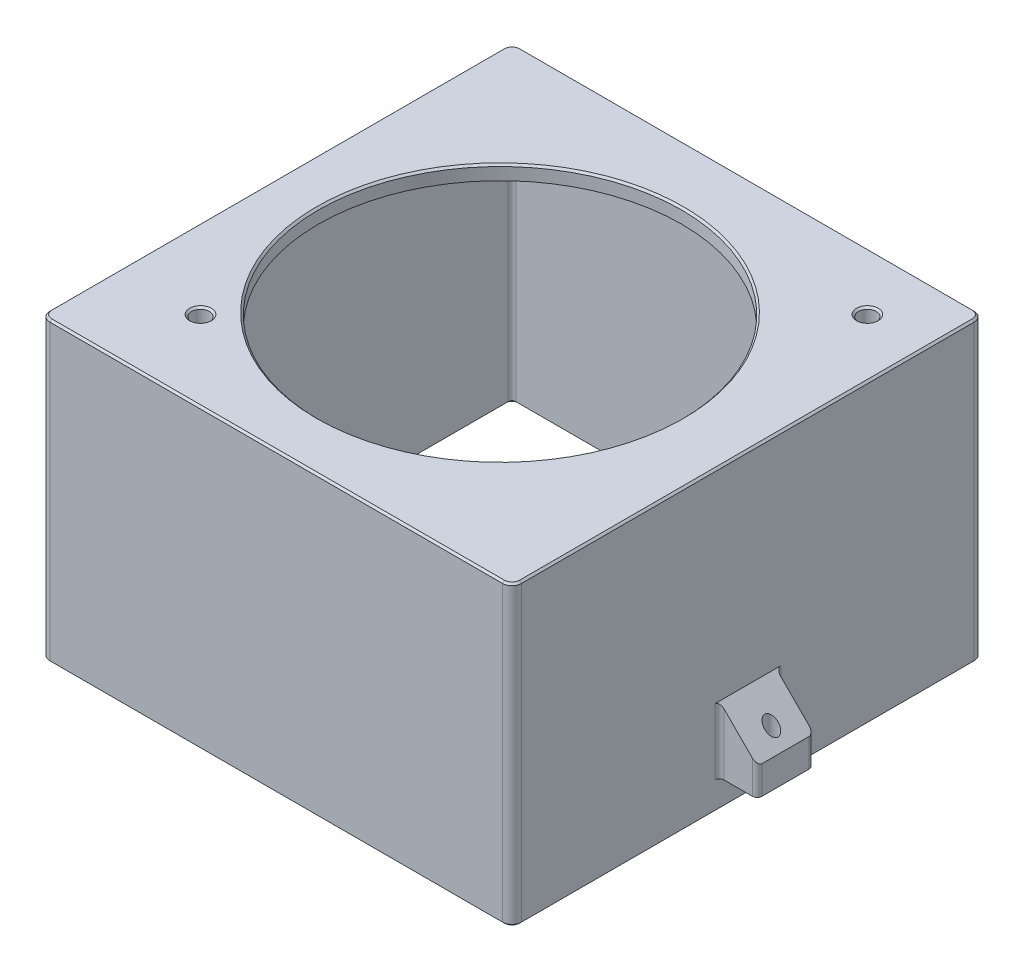
SolidWorks part; units mm, degrees
ref_plane "前视基准面" through (0, 0, 0) normal (0, 0, 1) x (1, 0, 0)
ref_plane "上视基准面" through (0, 0, 0) normal (0, 1, 0) x (1, 0, 0)
ref_plane "右视基准面" through (0, 0, 0) normal (1, 0, 0) x (0, 0, -1)
other "Configuration Table"
sketch "草图1" plane through (0, 0, 0) normal (0, 1, 0) x (1, 0, 0)
  line L0 (0, -100) -> (100, 0) construction
  line L1 (0, 0) -> (100, 0)
  line L2 (0, 0) -> (0, -100)
  line L3 (0, -100) -> (100, -100)
  line L4 (100, 0) -> (100, -100)
  circle A0 centre (16.9706, -83.0294) radius 1.9
  circle A1 centre (87.6812, -12.3188) radius 1.9
  dimension "D3" = 100
  dimension "D4" = 3.8
  dimension "D5" = 3.8
  dimension "D6" = 0
  dimension "D7" = 0
  dimension "D8" = 24
  dimension "D1" = 100
  dimension "D2" = 100
extrude "凸台-拉伸1" add sketch "草图1" along normal blind 3
sketch "草图2" plane through (0, 3, 0) normal (0, 1, 0) x (1, 0, 0)
  circle A0 centre (48.3812, -50.9188) radius 38.5
  dimension "D1" = 77
extrude "切除-拉伸1" cut sketch "草图2" against normal blind 10
sketch "草图3" plane through (0, 0, 0) normal (0, -1, 0) x (1, 0, 0)
  line L8 (3, 97) -> (3, 3)
  line L9 (3, 3) -> (97, 3)
  line L10 (97, 3) -> (97, 97)
  line L11 (97, 97) -> (3, 97)
  line L12 (3, 97) -> (3, 3)
  line L13 (3, 3) -> (97, 3)
  line L14 (97, 3) -> (97, 97)
  line L15 (97, 97) -> (3, 97)
  line L20 (0, 100) -> (0, 0)
  line L21 (0, 0) -> (100, 0)
  line L22 (100, 0) -> (100, 100)
  line L23 (100, 100) -> (0, 100)
  line L24 (0, 100) -> (0, 0)
  line L25 (0, 0) -> (100, 0)
  line L26 (100, 0) -> (100, 100)
  line L27 (100, 100) -> (0, 100)
  dimension "D1" = 3
  dimension "D2" = 0
extrude "凸台-拉伸2" add sketch "草图3" along normal blind 60
fillet "圆角1" radius 2 4 edges at (100, -28.5, 0) (100, -28.5, 100) (0, -28.5, 0) (0, -28.5, 100)
chamfer "倒角1" distance 0.4 angle 45 11 edges at (87.6812, 3, 14.2188) (99.4142, 3, 99.4142) (50, 3, 100) (0.5858, 3, 99.4142) (0, 3, 50) (0.5858, 3, 0.5858) (50, 3, 0) (99.4142, 3, 0.5858) (100, 3, 50) (16.9706, 3, 84.9294) (48.3812, 3, 89.4188)
fillet "圆角2" radius 0.8 8 edges at (50, 0, 97) (97, 0, 50) (50, 0, 3) (3, 0, 50) (3, -30, 3) (97, -30, 3) (97, -30, 97) (3, -30, 97)
chamfer "倒角2" distance 0.4 angle 45 16 edges at (3.2343, -60, 3.2343) (50, -60, 3) (96.7657, -60, 3.2343) (97, -60, 50) (96.7657, -60, 96.7657) (50, -60, 97) (3.2343, -60, 96.7657) (3, -60, 50) (0.5858, -60, 0.5858) (0, -60, 50) (0.5858, -60, 99.4142) (50, -60, 100) (99.4142, -60, 99.4142) (100, -60, 50) (99.4142, -60, 0.5858) (50, -60, 0)
ref_plane "基准面1" through (0, -54, 0) normal (0, -1, 0) x (-1, 0, 0)
sketch "草图4" plane through (0, -54, 0) normal (0, -1, 0) x (-1, 0, 0)
  line L0 (-100, -98) -> (-100, -2) construction
  line L5 (-100, -56) -> (-108, -56)
  line L6 (-100, -56) -> (-100, -44)
  line L7 (-100, -44) -> (-108, -44)
  line L8 (-108, -56) -> (-108, -44)
  line L9 (0, -2) -> (0, -98) construction
  line L10 (0, -56) -> (8, -56)
  line L11 (0, -56) -> (0, -44)
  line L12 (0, -44) -> (8, -44)
  line L13 (8, -56) -> (8, -44)
  line L14 (-0.4, -98) -> (-0.4, -2) construction
  point P12 (-100, -50)
  point P13 (-100, -50)
  point P14 (0, -50)
  point P17 (-0.4, -50)
  dimension "D1" = 0
  dimension "D2" = 0
  dimension "D3" = 12
  dimension "D4" = 12
  dimension "D5" = 8
  dimension "D6" = 8
extrude "凸台-拉伸3" add sketch "草图4" against normal blind 6
chamfer "倒角3" distance 8 angle 45 2 edges at (0, -48, 50) (100, -48, 50)
sketch "草图5" plane through (0, -54, 0) normal (0, -1, 0) x (-1, 0, 0)
  line L0 (8, -56) -> (8, -44) construction
  line L1 (-108, -44) -> (-108, -56) construction
  circle A0 centre (5, -50) radius 1.4
  circle A1 centre (-105, -50) radius 1.4
  dimension "D1" = 2.8
  dimension "D2" = 3
  dimension "D3" = 2.8
  dimension "D4" = 3
extrude "切除-拉伸2" cut sketch "草图5" against normal through all
fillet "圆角3" radius 1 8 edges at (100, -47, 56) (100, -47, 44) (0, -47, 44) (0, -47, 56) (-8, -51, 44) (-8, -51, 56) (108, -51, 56) (108, -51, 44)
